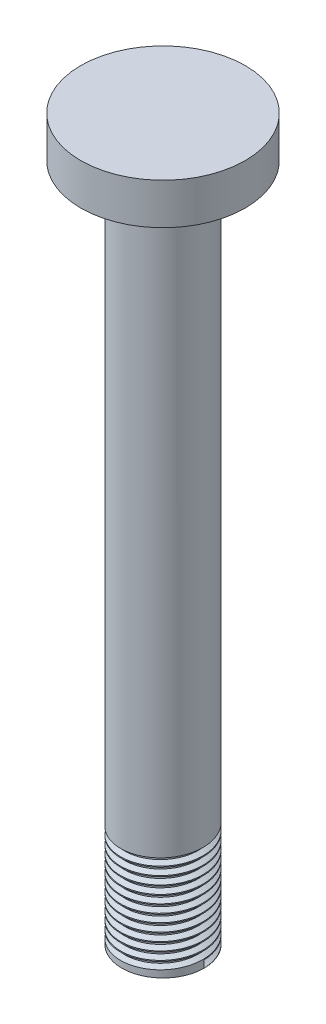
SolidWorks part; units mm, degrees
ref_plane "Front Plane" through (0, 0, 0) normal (0, 0, 1) x (1, 0, 0)
ref_plane "Top Plane" through (0, 0, 0) normal (0, 1, 0) x (1, 0, 0)
ref_plane "Right Plane" through (0, 0, 0) normal (1, 0, 0) x (0, 0, -1)
sketch "Sketch1" plane through (0, 0, 0) normal (0, 1, 0) x (1, 0, 0)
  circle A1 centre (0, 0) radius 4
  dimension "D2" = 8
extrude "Boss-Extrude1" add sketch "Sketch1" along normal blind 2
sketch "Sketch2" plane through (0, 0, 0) normal (0, -1, 0) x (1, 0, 0)
  circle A0 centre (0, 0) radius 2
  dimension "D1" = 4
extrude "Boss-Extrude2" add sketch "Sketch2" along normal blind 33
thread "Thread1" pitch 0.3969 method cut profile "Thread Profile1" start angle 0, offset 0, length 5, pitch 0.3969, diameter 4
ref_plane "Plane1" through (2, -33, 0) normal (0, 0, 1) x (1, 0, 0)
sketch "Thread Profile1" plane through (2, -33, 0) normal (0, 0, 1) x (1, 0, 0)
  line L0 (0, 0) -> (0, 0.3969) construction
  line L11 (0, 0) -> (0, 0.3473)
  line L12 (0, 0.3473) -> (-0.2148, 0.2232)
  line L13 (-0.2148, 0.2232) -> (-0.2148, 0.124)
  line L15 (-0.2148, 0.124) -> (0, 0)
  line L17 (-0.2148, 0.1736) -> (0, 0.1736) construction
  point P2 (0, 0)
  dimension "Pitch" = 0.3969
  dimension "Profile_Angle" = 60
  dimension "Profile_Land" = 0.0992
  dimension "Profile_Height" = 0.2148
